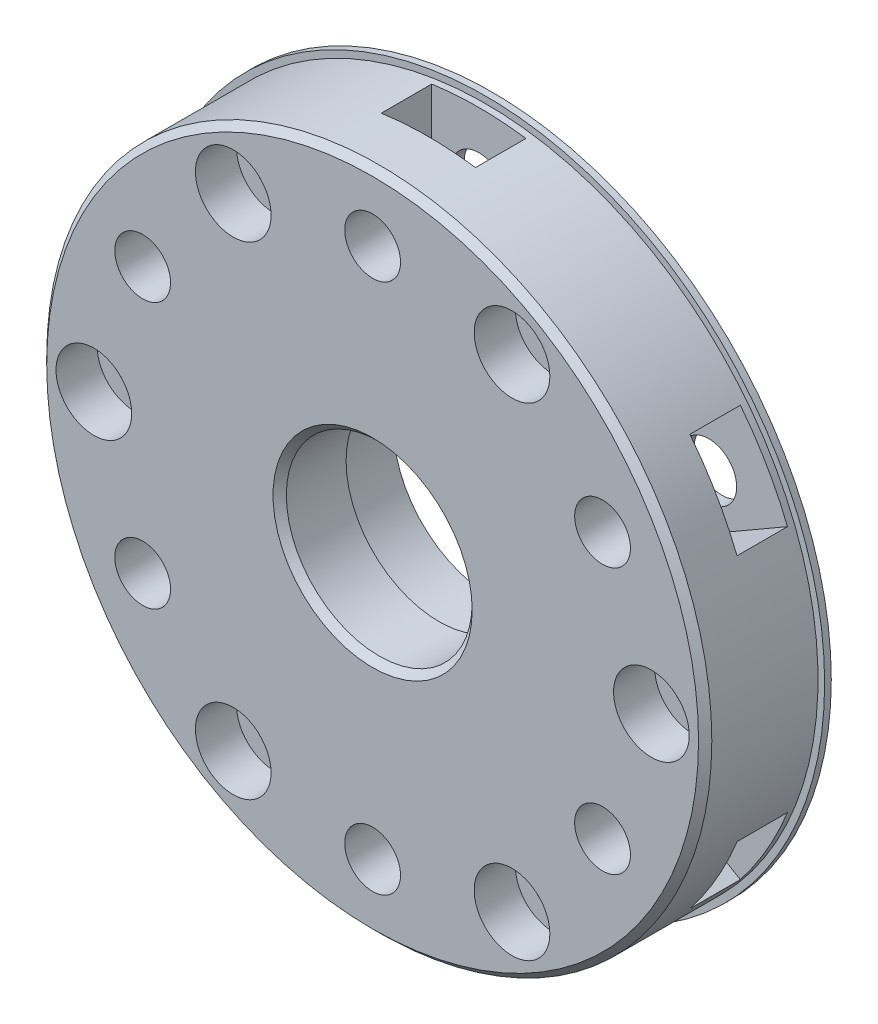
SolidWorks part; units mm, degrees
material "ABS"
ref_plane "Front Plane" through (0, 0, 0) normal (0, 0, 1) x (1, 0, 0)
ref_plane "Top Plane" through (0, 0, 0) normal (0, 1, 0) x (1, 0, 0)
ref_plane "Right Plane" through (0, 0, 0) normal (1, 0, 0) x (0, 0, -1)
sketch "Output Master Sketch" plane through (0, 0, 0) normal (0, 0, 1) x (1, 0, 0)
  circle A0 centre (0, 0) radius 21 construction
  circle A1 centre (21, 0) radius 2.85 construction
  circle A2 centre (10.5, -18.1865) radius 2.85 construction
  circle A3 centre (-10.5, -18.1865) radius 2.85 construction
  circle A4 centre (-21, 0) radius 2.85 construction
  circle A5 centre (-10.5, 18.1865) radius 2.85 construction
  circle A6 centre (10.5, 18.1865) radius 2.85 construction
  circle A7 centre (0, 0) radius 25.05
  point P17 (0, 0)
extrude "Boss-Extrude1" add sketch "Output Master Sketch" along normal blind 9
sketch "Sketch4" plane through (0, 0, 0) normal (0, 0, 1) x (1, 0, 0)
  circle A0 centre (21, 0) radius 2.85
  circle A1 centre (21, 0) radius 2.85 construction
  circle A2 centre (10.5, -18.1865) radius 2.85
  circle A3 centre (-10.5, -18.1865) radius 2.85
  circle A4 centre (-21, 0) radius 2.85
  circle A5 centre (-10.5, 18.1865) radius 2.85
  circle A6 centre (10.5, 18.1865) radius 2.85
  point P17 (0, 0)
  dimension "D1" = 6
extrude "Cut-Extrude1" cut sketch "Sketch4" along normal blind 4
sketch "Sketch5" plane through (0, 0, 0) normal (0, 0, -1) x (-1, 0, 0)
  circle A0 centre (0, 0) radius 25.05
  circle A1 centre (0, 0) radius 25.55
  circle A2 centre (0, 0) radius 25.05 construction
  dimension "D1" = 0.5
extrude "Boss-Extrude2" add sketch "Sketch5" against normal blind 0.5
sketch "Sketch6" plane through (0, 0, 0) normal (0, 0, -1) x (-1, 0, 0)
  circle A0 centre (-21, 0) radius 1.55
  circle A1 centre (-10.5, 18.1865) radius 1.55
  circle A2 centre (10.5, 18.1865) radius 1.55
  circle A3 centre (21, 0) radius 1.55
  circle A4 centre (10.5, -18.1865) radius 1.55
  circle A5 centre (-10.5, -18.1865) radius 1.55
  point P15 (0, 0)
  dimension "D1" = 3.1
  dimension "D2" = 6
extrude "Cut-Extrude2" cut sketch "Sketch6" against normal through all
sketch "Sketch7" plane through (0, 0, 9) normal (0, 0, 1) x (1, 0, 0)
  circle A0 centre (-21, 0) radius 2.85
  circle A1 centre (-10.5, 18.1865) radius 2.85
  circle A2 centre (10.5, 18.1865) radius 2.85
  circle A3 centre (21, 0) radius 2.85
  circle A4 centre (10.5, -18.1865) radius 2.85
  circle A5 centre (-10.5, -18.1865) radius 2.85
  point P16 (0, 0)
  dimension "D1" = 5.7
  dimension "D2" = 6
extrude "Cut-Extrude3" cut sketch "Sketch7" against normal blind 3.1
chamfer "Chamfer1" distance 0.5 angle 45 1 edges at (25.05, 0, 9)
sketch "Sketch8" plane through (0, 0, 0) normal (0, 0, -1) x (-1, 0, 0)
  circle A0 centre (0, 0) radius 7
  dimension "D1" = 14
extrude "Cut-Extrude4" cut sketch "Sketch8" against normal blind 10
sketch "Sketch9" plane through (0, 0, 0) normal (0, 0, -1) x (-1, 0, 0)
  circle A0 centre (0, 0) radius 7.425
  dimension "D1" = 14.85
extrude "Cut-Extrude5" cut sketch "Sketch9" against normal blind 4
sketch "Sketch10" plane through (0, 0, 9) normal (0, 0, 1) x (1, 0, 0)
  line L1 (0, 20) -> (-17.3205, 10) construction
  line L2 (-17.3205, 10) -> (-17.3205, -10) construction
  line L3 (-17.3205, -10) -> (0, -20) construction
  line L4 (0, -20) -> (17.3205, -10) construction
  line L5 (17.3205, -10) -> (17.3205, 10) construction
  line L6 (17.3205, 10) -> (0, 20) construction
  circle A0 centre (0, 0) radius 20 construction
  circle A1 centre (0, 20) radius 2.1
  circle A2 centre (17.3205, 10) radius 2.1
  circle A3 centre (17.3205, -10) radius 2.1
  circle A4 centre (0, -20) radius 2.1
  circle A5 centre (-17.3205, -10) radius 2.1
  circle A6 centre (-17.3205, 10) radius 2.1
  point P22 (0, 0)
  dimension "D1" = 40
  dimension "D2" = 4.2
  dimension "D3" = 6
extrude "M4 Thru" cut sketch "Sketch10" against normal through all
chamfer "Chamfer3" distance 0.5 angle 45 1 edges at (7, 0, 9)
sketch "Sketch11" plane through (0, 0, 9) normal (0, 0, 1) x (1, 0, 0)
  line L1 (0, 24.0992) -> (-3.55, 22.0496)
  line L2 (-3.55, 22.0496) -> (-3.55, 17.9504)
  line L3 (-3.55, 17.9504) -> (0, 15.9008)
  line L4 (0, 15.9008) -> (3.55, 17.9504)
  line L5 (3.55, 17.9504) -> (3.55, 22.0496)
  line L6 (3.55, 22.0496) -> (0, 24.0992)
  circle A0 centre (0, 20) radius 3.55 construction
  dimension "D1" = 7.1
extrude "M4 Hexnut Cut" cut sketch "Sketch11" along normal blind 3.8 from offset 8 offset against normal yes
ref_plane "Plane2" through (0, 22.0496, 0) normal (0, 1, 0) x (1, 0, 0)
sketch "Sketch12" plane through (0, 22.0496, 0) normal (0, 1, 0) x (1, 0, 0)
  line L1 (-3.55, -1) -> (3.55, -1)
  line L2 (-3.55, -1) -> (-3.55, -4.8)
  line L3 (-3.55, -4.8) -> (3.55, -4.8)
  line L4 (3.55, -1) -> (3.55, -4.8)
extrude "M4 Hexnut Slot" cut sketch "Sketch12" along normal through all contours L2 L1 L4 L3
pattern_circular "M4 Hexnut Pattern" count 6 over 360 about axis through (0, 0, 10) along (0, 0, -1) of "M4 Hexnut Cut", "M4 Hexnut Slot" reverse direction yes
